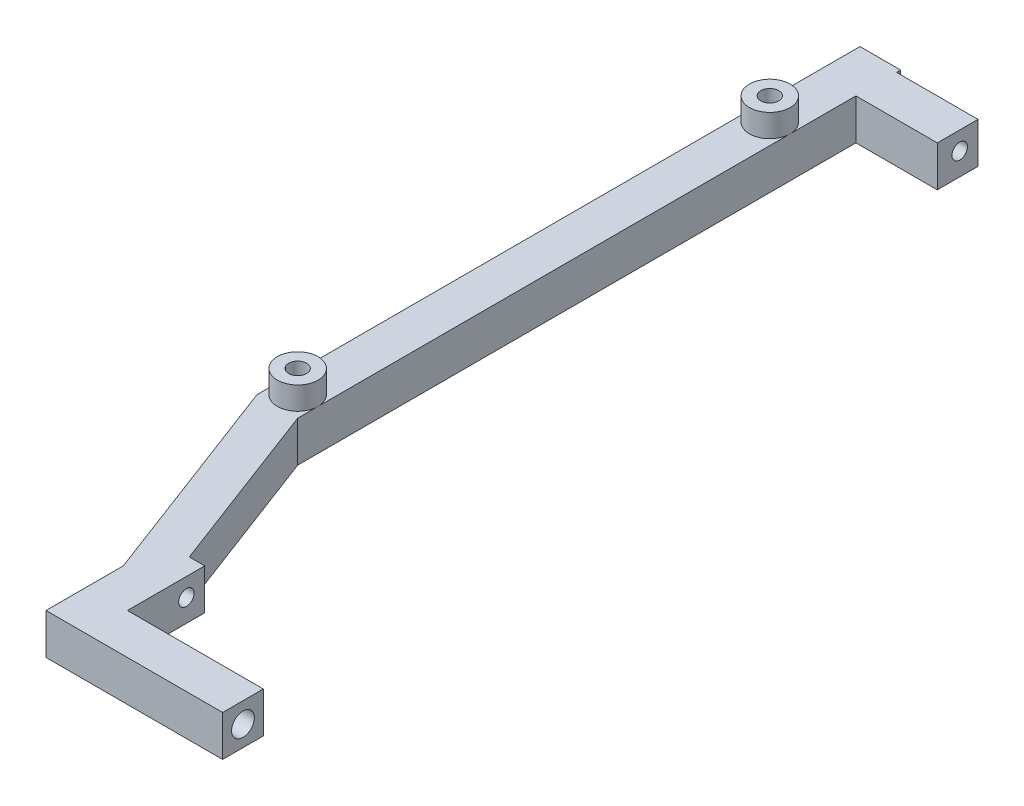
SolidWorks part; units mm, degrees
ref_plane "Front Plane" through (0, 0, 0) normal (0, 0, 1) x (1, 0, 0)
ref_plane "Top Plane" through (0, 0, 0) normal (0, 1, 0) x (1, 0, 0)
ref_plane "Right Plane" through (0, 0, 0) normal (1, 0, 0) x (0, 0, -1)
sketch "Sketch1" plane through (0, 0, 0) normal (0, 0, 1) x (1, 0, 0)
  line L1 (-2.5, 2.5) -> (2.5, 2.5)
  line L2 (-2.5, 2.5) -> (-2.5, -2.5)
  line L3 (-2.5, -2.5) -> (2.5, -2.5)
  line L4 (2.5, 2.5) -> (2.5, -2.5)
  line L5 (-2.5, 2.5) -> (2.5, -2.5) construction
  line L6 (-2.5, -2.5) -> (2.5, 2.5) construction
  point P0 (0, 0)
  dimension "D1" = 5
  dimension "D2" = 5
extrude "Boss-Extrude1" add sketch "Sketch1" along normal blind 74.08
sketch "Sketch2" plane through (0, 0, 0) normal (0, 0, -1) x (-1, 0, 0)
  circle A0 centre (0, 0) radius 1.4
  dimension "D1" = 2.8
extrude "Cut-Extrude1" cut sketch "Sketch2" against normal blind 10
sketch "Sketch3" plane through (2.5, 0, 0) normal (1, 0, 0) x (0, 0, -1)
  line L0 (-74.08, 2.5) -> (0, 2.5) construction
  line L1 (-0.5, 2.5) -> (-5.5, 2.5)
  line L2 (-0.5, 2.5) -> (-0.5, -2.5)
  line L3 (-0.5, -2.5) -> (-5.5, -2.5)
  line L4 (-5.5, 2.5) -> (-5.5, -2.5)
  line L5 (-74.08, -2.5) -> (0, -2.5) construction
  line L7 (0, -2.5) -> (0, 2.5) construction
  dimension "D1" = 5
  dimension "D2" = 0.5
extrude "Boss-Extrude2" add sketch "Sketch3" along normal blind 10
sketch "Sketch4" plane through (12.5, 0, 0) normal (1, 0, 0) x (0, 0, -1)
  line L0 (0, 2.5) -> (-5.5, -2) construction
  line L1 (-5.5, 2.5) -> (-5.5, -2.5) construction
  line L2 (-5.5, -2.5) -> (-0.5, -2.5) construction
  circle A0 centre (-2.75, 0.25) radius 0.95
  dimension "D1" = 1.9
  dimension "D2" = 0.5
extrude "Cut-Extrude2" cut sketch "Sketch4" against normal blind 5
sketch "Sketch5" plane through (0, 2.5, 0) normal (0, 1, 0) x (1, 0, 0)
  line L0 (0, -74.08) -> (0, 0) construction
  line L1 (-2.5, -69.08) -> (2.5, -74.08) construction
  line L2 (2.5, -74.08) -> (2.5, -5.5) construction
  line L3 (2.5, 0) -> (-2.5, 0) construction
  circle A0 centre (0, -13.58) radius 2.5
  circle A1 centre (0, -71.58) radius 2.5
  circle A2 centre (0, -13.58) radius 1.1
  circle A3 centre (0, -71.58) radius 1.1
  dimension "D1" = 2.2
  dimension "D2" = 13.58
extrude "Boss-Extrude3" add sketch "Sketch5" along normal blind 2.8
sketch "Sketch6" plane through (12.5, 0, 0) normal (1, 0, 0) x (0, 0, -1)
  line L6 (-95.5, -2.5) -> (-95.5, 2.5)
  line L7 (-95.5, 2.5) -> (-100.5, 2.5)
  line L8 (-100.5, 2.5) -> (-100.5, -2.5)
  line L9 (-100.5, -2.5) -> (-95.5, -2.5)
  line L10 (-0.5, -2.5) -> (-0.5, 2.5)
  line L11 (-0.5, 2.5) -> (-5.5, 2.5)
  line L12 (-5.5, 2.5) -> (-5.5, -2.5)
  line L13 (-5.5, -2.5) -> (-0.5, -2.5)
  line L14 (-0.5, -2.5) -> (-0.5, 2.5) construction
  line L15 (-0.5, 2.5) -> (-5.5, 2.5) construction
  line L16 (-5.5, 2.5) -> (-5.5, -2.5) construction
  line L17 (-5.5, -2.5) -> (-0.5, -2.5) construction
  circle A0 centre (-2.75, 0.25) radius 0.95 construction
  circle A1 centre (-2.75, 0.25) radius 0.95 construction
  circle A2 centre (-97.75, 0.25) radius 0.95
  point P7 (0, 0)
  dimension "D1" = 0
  dimension "D2" = 2
extrude "Boss-Extrude4" add sketch "Sketch6" against normal blind 5 separate body
sketch "Sketch7" plane through (0, 2.5, 0) normal (0, 1, 0) x (1, 0, 0)
  line L0 (7.5, -100.5) -> (-2.5, -74.08)
  line L1 (-2.5, -74.08) -> (2.5, -74.08)
  line L2 (2.5, -74.08) -> (10.6075, -95.5)
  line L5 (10.6075, -95.5) -> (7.5, -95.5)
  line L6 (7.5, -95.5) -> (7.5, -100.5)
  line L7 (7.5, -95.5) -> (12.5, -95.5) construction
  line L8 (10.6075, -95.5) -> (12.5, -100.5) construction
extrude "Boss-Extrude5" add sketch "Sketch7" against normal up to surface (5 mm away) from surface up to face at (10, -2.5, 98) starting at face at (0, 2.5, 42.58)
sketch "Sketch8" plane through (0, 0, 0) normal (0, 1, 0) x (1, 0, 0)
  line L0 (7.5, -100.5) -> (7.5, -110)
  line L1 (7.5, -110) -> (29.2, -110)
  line L2 (29.2, -110) -> (29.2, -105)
  line L3 (29.2, -105) -> (12.5, -105)
  line L4 (12.5, -105) -> (12.5, -100.5)
  line L5 (7.5, -100.5) -> (12.5, -100.5) construction
  line L6 (12.5, -95.5) -> (12.5, -100.5) construction
  line L7 (7.5, -100.5) -> (12.5, -100.5)
  dimension "D1" = 4.5
  dimension "D2" = 5
  dimension "D3" = 16.7
extrude "Boss-Extrude6" add sketch "Sketch8" against normal up to surface (2.5 mm away) from surface up to face at (6.0923, -2.5, 46.0133) starting at face at (5.3884, 2.5, 85.7275)
sketch "Sketch9" plane through (29.2, 0, 0) normal (1, 0, 0) x (0, 0, -1)
  line L0 (-110, 2.5) -> (-105, -2.5) construction
  line L1 (-105, -2.5) -> (-105, 2.5) construction
  line L2 (-105, -2.5) -> (-110, -2.5) construction
  circle A0 centre (-107.5, 0) radius 1.4
  dimension "D2" = 2.8
  dimension "D1" = 0
extrude "Cut-Extrude3" cut sketch "Sketch9" against normal blind 10
